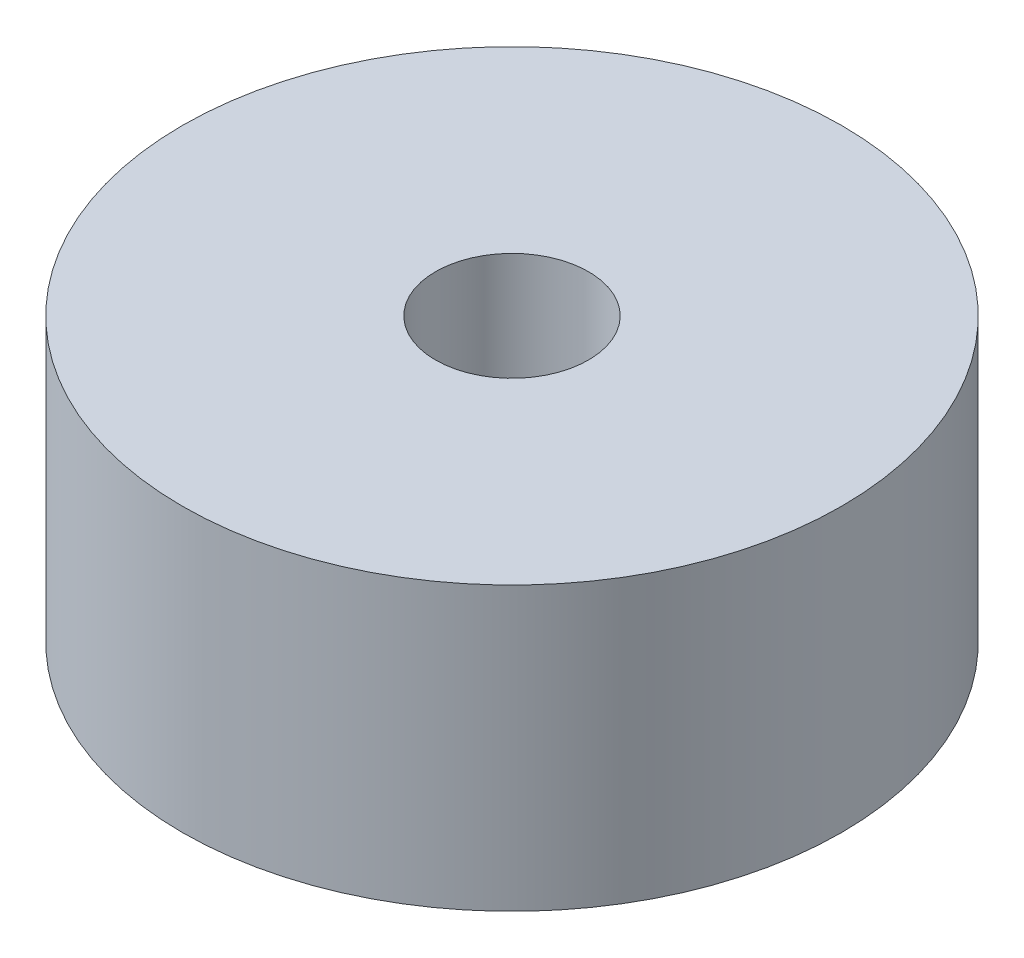
SolidWorks part; units mm, degrees
ref_plane "前视基准面" through (0, 0, 0) normal (0, 0, 1) x (1, 0, 0)
ref_plane "上视基准面" through (0, 0, 0) normal (0, 1, 0) x (1, 0, 0)
ref_plane "右视基准面" through (0, 0, 0) normal (1, 0, 0) x (0, 0, -1)
other "Configuration Table"
sketch "草图1" plane through (0, 0, 0) normal (0, 1, 0) x (1, 0, 0)
  circle A0 centre (0, 0) radius 5.6
  circle A1 centre (0, 0) radius 1.3
  dimension "D1" = 2.6
  dimension "D2" = 11.2
extrude "凸台-拉伸1" add sketch "草图1" along normal blind 4.8 contours A0 | A1
